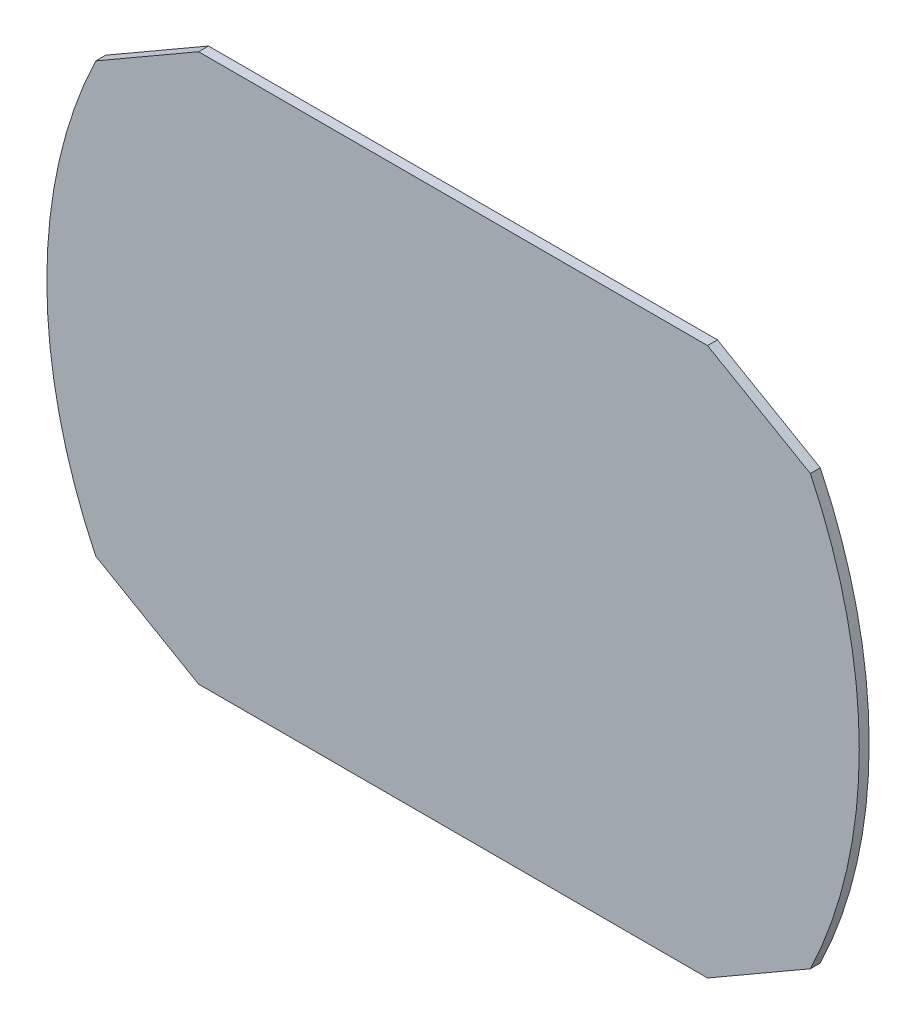
SolidWorks part; units mm, degrees
ref_plane "Front Plane" through (0, 0, 0) normal (0, 0, 1) x (1, 0, 0)
ref_plane "Top Plane" through (0, 0, 0) normal (0, 1, 0) x (1, 0, 0)
ref_plane "Right Plane" through (0, 0, 0) normal (1, 0, 0) x (0, 0, -1)
sketch "Sketch1" plane through (0, 0, 0) normal (0, 0, 1) x (1, 0, 0)
  line L0 (-65, 90) -> (-108.3013, 65)
  line L1 (-65, -90) -> (65, -90)
  line L3 (-65, 90) -> (65, 90)
  line L5 (-65, -90) -> (65, 90) construction
  line L6 (-65, 90) -> (65, -90) construction
  line L7 (-65, -90) -> (-108.3013, -65)
  line L8 (65, 90) -> (108.3013, 65)
  line L9 (65, -90) -> (108.3013, -65)
  arc A1 (-108.3013, 65) -> (-108.3013, -65) centre (26.8838, 0) ccw
  arc A4 (108.3013, 65) -> (108.3013, -65) centre (-26.8838, 0) cw
  point P0 (0, 0)
  point P7 (0, -90)
  dimension "D13" = 150
  dimension "D14" = 150
  dimension "D1" = 180
  dimension "D2" = 130
  dimension "D3" = 130
  dimension "D4" = 0
  dimension "D5" = 50
  dimension "D6" = 150
  dimension "D7" = 50
  dimension "D8" = 150
  dimension "D9" = 50
  dimension "D10" = 150
  dimension "D11" = 50
  dimension "D12" = 150
extrude "Boss-Extrude1" add sketch "Sketch1" along normal blind 3
sketch "Sketch2" plane through (0, 0, 3) normal (0, 0, 1) x (1, 0, 0)
  line L0 (-70.9808, 75) -> (70.9808, 75)
  line L1 (70.9808, 75) -> (103.1162, 56.4466)
  line L3 (65, 90) -> (-65, 90) construction
  line L4 (-70.9808, -75) -> (70.9808, -75)
  line L5 (70.9808, -75) -> (103.1162, -56.4466)
  line L6 (-65, -90) -> (65, -90) construction
  line L7 (108.3013, 65) -> (65, 90) construction
  line L8 (65, -90) -> (108.3013, -65) construction
  line L9 (-70.9808, 75) -> (-103.1162, 56.4466)
  line L10 (-70.9808, -75) -> (-103.1162, -56.4466)
  line L13 (-65, 90) -> (-108.3013, 65) construction
  line L15 (-108.3013, -65) -> (-65, -90) construction
  line L16 (-103.1162, 56.4466) -> (-103.1162, -56.4466)
  line L17 (103.1162, 56.4466) -> (103.1162, -56.4466)
  arc A0 (-108.3013, 65) -> (-108.3013, -65) centre (26.8838, 0) ccw construction
  arc A1 (108.3013, -65) -> (108.3013, 65) centre (-26.8838, 0) ccw construction
  point P24 (-123.1162, 0)
  point P28 (123.1162, 0)
  dimension "D1" = 15
  dimension "D2" = 10
  dimension "D3" = 20
  dimension "D4" = 15
  dimension "D5" = 20
  dimension "D7" = 10
  dimension "D8" = 10
  dimension "D10" = 10
sketch "Sketch3" plane through (0, 0, 0) normal (1, 0, 0) x (0, 0, -1)
  line L0 (-3, 90) -> (0, 90) construction
  line L1 (2, 85) -> (5.5, 85)
  line L2 (2, 85) -> (2, -85)
  line L3 (2, -85) -> (5.5, -85)
  line L4 (5.5, 85) -> (5.5, -85)
  line L5 (-3, -90) -> (0, -90) construction
  line L6 (-3, 65) -> (-3, -65) construction
  line L8 (-8.5, 82) -> (-5, 82)
  line L9 (-8.5, 82) -> (-8.5, -85)
  line L10 (-8.5, -85) -> (-5, -85)
  line L11 (-5, 82) -> (-5, -85)
  line L12 (0, -65) -> (0, 65) construction
  dimension "D1" = 5
  dimension "D2" = 5
  dimension "D3" = 5
  dimension "D4" = 3.5
  dimension "D5" = 8
  dimension "D6" = 5
  dimension "D7" = 5
  dimension "D8" = 3.5
extrude "Cut-Extrude4" [suppressed] cut sketch "Sketch2" against normal through all both and the other way through all
extrude "Cut-Extrude5" [suppressed] cut sketch "Sketch3" against normal through all both and the other way through all
sketch "Sketch7" [suppressed] plane through (0, 0, 0) normal (1, 0, 0) x (0, 0, -1)
  line L0 (-231.5, 65) -> (-231.5, -65) construction
  line L1 (-226.5, 45) -> (-13.5, 45)
  line L2 (-226.5, 45) -> (-226.5, 50)
  line L3 (-226.5, 50) -> (-13.5, 50)
  line L4 (-13.5, 45) -> (-13.5, 50)
  line L5 (-226.5, 45) -> (-13.5, 50) construction
  line L6 (-226.5, 50) -> (-13.5, 45) construction
  line L7 (-8.5, -65) -> (-8.5, 65) construction
  line L8 (0, 75) -> (-3, 75) construction
  point P0 (-120, 47.5)
  dimension "D1" = 5
  dimension "D2" = 5
  dimension "D3" = 5
  dimension "D4" = 25
extrude "Boss-Extrude4" [suppressed] add sketch "Sketch7" along normal up to surface and the other way up to surface
chamfer "Chamfer7" [suppressed] distance 6 angle 45
sketch "Sketch8" [suppressed] plane through (0, -75, 0) normal (0, 1, 0) x (1, 0, 0)
  line L0 (-78.8564, -8.5) -> (-108.3013, -8.5) construction
  line L1 (-2.5, -226.5) -> (2.5, -226.5)
  line L2 (-2.5, -226.5) -> (-2.5, -13.5)
  line L3 (-2.5, -13.5) -> (2.5, -13.5)
  line L4 (2.5, -226.5) -> (2.5, -13.5)
  line L5 (-2.5, -226.5) -> (2.5, -13.5) construction
  line L6 (-2.5, -13.5) -> (2.5, -226.5) construction
  line L7 (-108.3013, -231.5) -> (-73.6603, -231.5) construction
  point P0 (0, -120)
  dimension "D1" = 5
  dimension "D2" = 5
  dimension "D3" = 5
extrude "Boss-Extrude5" [suppressed] add sketch "Sketch8" along normal up to surface (120 mm away)
chamfer "Chamfer8" [suppressed] distance 6 angle 45
sketch "Sketch10" [suppressed] plane through (0, 0, 0) normal (1, 0, 0) x (0, 0, -1)
  line L0 (-240, -90) -> (0, -90) construction
  line L1 (-132.5, -75) -> (-107.5, -75)
  line L2 (-132.5, -75) -> (-132.5, -69)
  line L3 (-132.5, -69) -> (-107.5, -69)
  line L4 (-107.5, -75) -> (-107.5, -69)
  line L5 (-132.5, -75) -> (-107.5, -69) construction
  line L6 (-132.5, -69) -> (-107.5, -75) construction
  line L7 (-13.5, -75) -> (-226.5, -75) construction
  line L8 (-226.5, -69) -> (-13.5, -69) construction
  point P0 (-120, -72)
  point P7 (-120, -90)
  point P8 (-120, -75)
  dimension "D1" = 0
  dimension "D2" = 0
  dimension "D3" = 0
  dimension "D4" = 25
extrude "Cut-Extrude6" [suppressed] cut sketch "Sketch10" against normal blind 176 and the other way blind 23
sketch "Sketch12" [suppressed] plane through (0, 0, 0) normal (1, 0, 0) x (0, 0, -1)
  line L5 (-10, -64) -> (-230, -64)
  line L6 (-230, -64) -> (-230, -75)
  line L7 (-230, -75) -> (-14, -75)
  line L8 (-14, -75) -> (-14, -69)
  line L9 (-14, -69) -> (11, -69)
  line L10 (11, -69) -> (11, -75)
  line L11 (11, -75) -> (-10, -75)
  line L13 (-231.5, 56.4466) -> (-231.5, -56.4466) construction
  line L15 (0, -75) -> (-3, -75) construction
  line L16 (-3, -90) -> (0, -90) construction
  line L17 (-10, -75) -> (-10, -64)
  line L18 (-8.5, -85) -> (-8.5, -65) construction
  point P16 (-1.5, -69)
  point P19 (-1.5, -90)
  dimension "D1" = 11
  dimension "D2" = 1.5
  dimension "D3" = 1.5
  dimension "D4" = 0
  dimension "D5" = 0
  dimension "D6" = 25
  dimension "D7" = 6
  dimension "D8" = 6
extrude "Boss-Extrude6" [suppressed] add sketch "Sketch12" against normal blind 90
fillet "Fillet1" [suppressed] radius 10
fillet "Fillet2" [suppressed] radius 10
sketch "Sketch13" [suppressed] plane through (0, 0, 0) normal (1, 0, 0) x (0, 0, -1)
  line L0 (-3, 90) -> (0, 90) construction
  line L1 (0, 75) -> (-3, 75) construction
  circle A0 centre (-54.85, 62) radius 2.5
  circle A1 centre (51.85, 62) radius 2.5
  circle A2 centre (-1.5, 62) radius 2.5
  point P6 (-1.5, 90)
  dimension "D1" = 53.35
  dimension "D5" = 5
  dimension "D6" = 5
  dimension "D7" = 5
  dimension "D2" = 53.35
  dimension "D3" = 13
  dimension "D4" = 13
extrude "Cut-Extrude7" [suppressed] cut sketch "Sketch13" against normal through all
sketch "Sketch14" [suppressed] plane through (0, 50, 0) normal (0, 1, 0) x (1, 0, 0)
  line L0 (103.1162, -226.5) -> (-103.1162, -226.5) construction
  line L1 (-2.5, -226.5) -> (-2.5, -13.5) construction
  circle A0 centre (-52.5, -119.8) radius 2.5
  dimension "D1" = 5
  dimension "D2" = 106.7
  dimension "D3" = 50
extrude "Cut-Extrude8" [suppressed] cut sketch "Sketch14" against normal blind 47
sketch "Sketch15" [suppressed] plane through (-103.1162, 0, 0) normal (1, 0, 0) x (0, 0, -1)
  line L0 (-231.5, 56.4466) -> (-231.5, -56.4466) construction
  line L1 (-8.5, -56.4466) -> (-8.5, 56.4466) construction
  line L2 (-13.5, 39) -> (-226.5, 39) construction
  circle A0 centre (-172.99, 24) radius 2.5
  circle A1 centre (-67.25, 24) radius 2.5
  dimension "D1" = 58.51
  dimension "D3" = 5
  dimension "D4" = 5
  dimension "D2" = 58.75
  dimension "D5" = 15
extrude "Cut-Extrude9" [suppressed] cut sketch "Sketch15" against normal blind 36
sketch "Sketch16" [suppressed] plane through (0, -75, 0) normal (0, 1, 0) x (1, 0, 0)
  line L0 (70.9808, -8.5) -> (70.9808, -231.5) construction
  line L1 (23.5, -170) -> (29.5, -170)
  line L2 (23.5, -170) -> (23.5, -70)
  line L3 (23.5, -70) -> (29.5, -70)
  line L4 (29.5, -170) -> (29.5, -70)
  line L5 (8.5, -13.5) -> (8.5, -107.5) construction
  line L7 (39.5, -162.5) -> (59.5, -162.5)
  line L8 (39.5, -162.5) -> (39.5, -77.5)
  line L9 (39.5, -77.5) -> (59.5, -77.5)
  line L10 (59.5, -162.5) -> (59.5, -77.5)
  point P4 (23.5, -120)
  point P7 (70.9808, -120)
  point P14 (59.5, -120)
  dimension "D1" = 6
  dimension "D2" = 100
  dimension "D3" = 0
  dimension "D4" = 15
  dimension "D5" = 20
  dimension "D6" = 85
  dimension "D7" = 0
  dimension "D8" = 10
extrude "Cut-Extrude10" [suppressed] cut sketch "Sketch16" against normal blind 8
sketch "Sketch20" [suppressed] plane through (0, -75, 0) normal (0, 1, 0) x (1, 0, 0)
  line L0 (59.5, -77.5) -> (39.5, -77.5) construction
  line L1 (23, -70) -> (21, -70)
  line L2 (23, -70) -> (23, -170)
  line L3 (23, -170) -> (21, -170)
  line L4 (21, -70) -> (21, -170)
  line L5 (30, -70) -> (32, -70)
  line L6 (30, -70) -> (30, -170)
  line L7 (30, -170) -> (32, -170)
  line L8 (32, -70) -> (32, -170)
  line L9 (37.5, -77.5) -> (39, -77.5)
  line L10 (37.5, -77.5) -> (37.5, -162.5)
  line L11 (37.5, -162.5) -> (39, -162.5)
  line L12 (39, -77.5) -> (39, -162.5)
  line L13 (61.5, -162.5) -> (60, -162.5)
  line L14 (61.5, -162.5) -> (61.5, -77.5)
  line L15 (61.5, -77.5) -> (60, -77.5)
  line L16 (60, -162.5) -> (60, -77.5)
  line L17 (39.5, -162.5) -> (59.5, -162.5) construction
  line L18 (29.5, -70) -> (23.5, -70) construction
  line L19 (23.5, -170) -> (29.5, -170) construction
  line L20 (29.5, -170) -> (29.5, -70) construction
  line L21 (23.5, -70) -> (23.5, -170) construction
  line L22 (39.5, -77.5) -> (39.5, -162.5) construction
  line L23 (59.5, -162.5) -> (59.5, -77.5) construction
  dimension "D1" = 1.5
  dimension "D2" = 1.5
  dimension "D3" = 2
  dimension "D4" = 2
  dimension "D5" = 0.5
  dimension "D6" = 0.5
  dimension "D7" = 0.5
  dimension "D8" = 0.5
extrude "Boss-Extrude7" [suppressed] add sketch "Sketch20" along normal blind 8
sketch "Sketch21" [suppressed] plane through (0, 0, 170) normal (0, 0, 1) x (1, 0, 0)
  line L0 (22.5, -67) -> (21, -73.7542)
  line L1 (21, -67) -> (21, -75) construction
  line L2 (21, -73.7542) -> (21, -67)
  line L3 (21, -67) -> (22.5, -67)
  line L4 (30.5, -67) -> (32, -67)
  line L5 (32, -67) -> (32, -73.7542)
  line L6 (32, -67) -> (32, -75) construction
  line L7 (32, -73.7542) -> (30.5, -67)
  line L8 (38.5, -67) -> (37.5, -73.7542)
  line L9 (37.5, -67) -> (37.5, -75) construction
  line L10 (37.5, -73.7542) -> (37.5, -67)
  line L11 (37.5, -67) -> (38.5, -67)
  line L12 (60.5, -67) -> (61.5, -73.7542)
  line L13 (61.5, -67) -> (61.5, -75) construction
  line L14 (61.5, -73.7542) -> (61.5, -67)
  line L15 (61.5, -67) -> (60.5, -67)
  line L16 (21, -67) -> (23, -67) construction
  line L17 (30, -67) -> (32, -67) construction
  line L18 (37.5, -67) -> (39, -67) construction
  line L19 (60, -67) -> (61.5, -67) construction
  dimension "D1" = 1.5
  dimension "D2" = 1.5
  dimension "D3" = 1
  dimension "D4" = 1
extrude "Cut-Extrude11" [suppressed] cut sketch "Sketch21" against normal up to next
fillet "Fillet4" [suppressed] radius 0.25
fillet "Fillet5" [suppressed] radius 1
sketch "Sketch22" [suppressed] plane through (61.5, 0, 0) normal (1, 0, 0) x (0, 0, -1)
  line L0 (-162.5, -75) -> (-77.5, -75) construction
  line L1 (-130, -75) -> (-110, -75)
  line L2 (-130, -75) -> (-130, -65)
  line L3 (-130, -65) -> (-110, -65)
  line L4 (-110, -75) -> (-110, -65)
  point P6 (-120, -75)
  point P7 (-120, -75)
  dimension "D1" = 20
  dimension "D2" = 10
extrude "Cut-Extrude12" [suppressed] cut sketch "Sketch22" against normal blind 43
chamfer "Chamfer9" [suppressed] distance 1 angle 45
sketch "Sketch24" [suppressed] plane through (0, 50, 0) normal (0, 1, 0) x (1, 0, 0)
  line L0 (-17.9178, -104) -> (17.9178, -104)
  line L1 (103.1162, -13.5) -> (103.1162, -226.5) construction
  line L5 (-32.9693, -110.0691) -> (-29.9693, -110.0691)
  line L6 (-17.9178, -101.5752) -> (17.9178, -101.5752)
  line L7 (29.9693, -110.0691) -> (32.9693, -110.0691)
  arc A0 (-17.9178, -104) -> (-29.9693, -110.0691) centre (-17.9178, -119) ccw
  arc A1 (17.9178, -104) -> (29.9693, -110.0691) centre (17.9178, -119) cw
  arc A3 (-32.9693, -110.0691) -> (-17.9178, -101.5752) centre (-19.4178, -116.5) cw
  arc A4 (32.9693, -110.0691) -> (17.9178, -101.5752) centre (19.4178, -116.5) ccw
  point P3 (0, -104)
  point P6 (103.1162, -120)
  dimension "D3" = 15
  dimension "D4" = 15
  dimension "D5" = 1.5
  dimension "D7" = 15
  dimension "D8" = 15
  dimension "D11" = 3
  dimension "D12" = 3
  dimension "D1" = 0
  dimension "D2" = 16
  dimension "D6" = 2.5
  dimension "D9" = 1.5
  dimension "D10" = 2.5
extrude "Boss-Extrude8" [suppressed] add sketch "Sketch24" along normal blind 8
fillet "Fillet6" [suppressed] radius 1
fillet "Fillet7" [suppressed] radius 1
sketch "Sketch25" [suppressed] plane through (0, -64, 0) normal (0, 1, 0) x (1, 0, 0)
  line L0 (-90, -10) -> (-7.5993, -10) construction
  line L1 (-2.5, -13.5) -> (-2.5, -226.5) construction
  line L3 (-90, -230) -> (-7.5993, -230) construction
  circle A0 centre (-48.7997, -46.5) radius 35
  circle A1 centre (-48.7997, -120) radius 35
  circle A2 centre (-48.7997, -193.5) radius 35
  point P9 (-48.7997, -10)
  point P13 (-2.5, -120)
  dimension "D1" = 70
  dimension "D2" = 70
  dimension "D3" = 70
  dimension "D4" = 36.5
  dimension "D5" = 36.5
extrude "Cut-Extrude13" [suppressed] cut sketch "Sketch25" against normal blind 5
sketch "Sketch26" [suppressed] plane through (0, 50, 0) normal (0, 1, 0) x (1, 0, 0)
  line L0 (70.9808, -8.5) -> (70.9808, -231.5) construction
  line L1 (73.9808, -155) -> (98.9808, -155)
  line L2 (73.9808, -155) -> (73.9808, -85)
  line L3 (73.9808, -85) -> (98.9808, -85)
  line L4 (98.9808, -155) -> (98.9808, -85)
  line L5 (73.9808, -155) -> (98.9808, -85) construction
  line L6 (73.9808, -85) -> (98.9808, -155) construction
  line L7 (108.3013, -231.5) -> (108.3013, -8.5) construction
  point P0 (86.4808, -120)
  point P9 (108.3013, -120)
  dimension "D1" = 70
  dimension "D2" = 25
  dimension "D3" = 3
  dimension "D4" = 0
extrude "Cut-Extrude14" [suppressed] cut sketch "Sketch26" against normal blind 12.5 from offset 105 offset against normal yes
sketch "Sketch27" [suppressed] plane through (0, -67.5, 0) normal (0, 1, 0) x (1, 0, 0)
  line L0 (83.9711, -155) -> (98.9808, -155) construction
  line L1 (83.9711, -85) -> (73.9711, -85)
  line L2 (83.9711, -85) -> (83.9711, -155)
  line L3 (83.9711, -155) -> (73.9711, -155)
  line L4 (73.9711, -85) -> (73.9711, -155)
  dimension "D1" = 10
extrude "Boss-Extrude9" [suppressed] add sketch "Sketch27" against normal blind 9
fillet "Fillet8" [suppressed] radius 1
sketch "Sketch28" [suppressed] plane through (0, 0, 155) normal (0, 0, 1) x (1, 0, 0)
  line L0 (73.9711, -73.2735) -> (83.9711, -67.5)
  line L2 (73.9711, -73.2735) -> (73.9711, -67.5)
  line L3 (73.9711, -67.5) -> (83.9711, -67.5)
extrude "Cut-Extrude15" [suppressed] cut sketch "Sketch28" against normal blind 10 from offset 30 offset against normal yes
fillet "Fillet9" [suppressed] radius 1
fillet "Fillet10" [suppressed] radius 2
chamfer "Chamfer10" [suppressed] distance 1 angle 45
sketch "Sketch29" plane through (0, 0, 0) normal (0, 0, 1) x (1, 0, 0)
  line L1 (-135.4816, 0) -> (144.3449, 0)
  line L2 (-135.4816, 0) -> (-135.4816, -99.522)
  line L3 (-135.4816, -99.522) -> (144.3449, -99.522)
  line L4 (144.3449, 0) -> (144.3449, -99.522)
extrude "Cut-Extrude16" [suppressed] cut sketch "Sketch29" against normal through all both and the other way through all
sketch "Sketch30" [suppressed] plane through (0, 0, 0) normal (0, -1, 0) x (1, 0, 0)
  line L0 (-123.1162, 231.5) -> (-103.1162, 231.5) construction
  line L1 (-118.1162, 191.5) -> (-108.1162, 191.5)
  line L2 (-118.1162, 191.5) -> (-118.1162, 48.5)
  line L3 (-118.1162, 48.5) -> (-108.1162, 48.5)
  line L4 (-108.1162, 191.5) -> (-108.1162, 48.5)
  line L5 (108.1162, 191.5) -> (118.1162, 191.5)
  line L6 (108.1162, 191.5) -> (108.1162, 48.5)
  line L7 (108.1162, 48.5) -> (118.1162, 48.5)
  line L8 (118.1162, 191.5) -> (118.1162, 48.5)
  line L9 (-103.1162, 8.5) -> (-123.1162, 8.5) construction
  line L10 (103.1162, 231.5) -> (123.1162, 231.5) construction
  line L11 (123.1162, 8.5) -> (103.1162, 8.5) construction
  line L12 (-123.1162, 8.5) -> (-123.1162, 231.5) construction
  line L13 (-103.1162, 231.5) -> (-103.1162, 8.5) construction
  line L14 (103.1162, 226.5) -> (103.1162, 13.5) construction
  line L15 (123.1162, 231.5) -> (123.1162, 8.5) construction
  dimension "D1" = 40
  dimension "D2" = 40
  dimension "D3" = 40
  dimension "D4" = 40
  dimension "D5" = 5
  dimension "D6" = 5
  dimension "D7" = 5
  dimension "D8" = 5
extrude "Cut-Extrude17" [suppressed] cut sketch "Sketch30" against normal blind 20
chamfer "Chamfer11" [suppressed] distance 3 angle 45
sketch "Sketch32" [suppressed] plane through (0, 0, 3) normal (0, 0, 1) x (1, 0, 0)
  line L0 (-53, 90) -> (-53, 88)
  line L1 (65, 90) -> (-65, 90) construction
  line L2 (-53, 88) -> (-60, 88)
  line L3 (-60, 88) -> (-60, 84.5)
  line L4 (-60, 84.5) -> (-53, 84.5)
  line L5 (-53, 84.5) -> (-53, 82.5)
  line L6 (-53, 82.5) -> (-60, 82.5)
  line L7 (-60, 82.5) -> (-60, 75)
  line L8 (-70.9808, 75) -> (70.9808, 75) construction
  line L9 (-60, 75) -> (60, 75)
  line L10 (60, 75) -> (60, 82.5)
  line L11 (60, 82.5) -> (53, 82.5)
  line L12 (53, 82.5) -> (53, 84.5)
  line L13 (53, 84.5) -> (60, 84.5)
  line L14 (60, 84.5) -> (60, 88)
  line L15 (60, 88) -> (53, 88)
  line L16 (53, 88) -> (53, 90)
  line L17 (53, 90) -> (-53, 90)
  dimension "D1" = 12
  dimension "D2" = 5
  dimension "D3" = 7
  dimension "D4" = 5
  dimension "D5" = 2
  dimension "D6" = 2
  dimension "D7" = 3.5
  dimension "D8" = 2
  dimension "D9" = 2
  dimension "D10" = 3.5
extrude "Cut-Extrude19" [suppressed] cut sketch "Sketch32" against normal through all from offset 8.5 offset against normal yes
fillet "Fillet11" [suppressed] radius 1
sketch "Sketch33" plane through (0, 0, 3) normal (0, 0, 1) x (1, 0, 0)
  line L1 (65, 90) -> (-65, 90) construction
  circle A0 centre (0, 82.5) radius 2
  dimension "D1" = 7.5
  dimension "D2" = 4
extrude "Cut-Extrude20" [suppressed] cut sketch "Sketch33" against normal blind 4.5
chamfer "Chamfer12" [suppressed] distance 1 angle 45
sketch "Sketch34" plane through (0, 0, 0) normal (1, 0, 0) x (0, 0, -1)
  line L0 (0, 65) -> (0, 90) construction
  line L1 (-3, 90) -> (0, 90)
  line L2 (-3, 90) -> (-3, 83)
  line L3 (-3, 83) -> (0, 83)
  line L4 (0, 90) -> (0, 83)
  line L5 (0, -90) -> (0, -65) construction
  line L7 (-3, -90) -> (0, -90)
  line L8 (-3, -90) -> (-3, -83)
  line L9 (-3, -83) -> (0, -83)
  line L10 (0, -90) -> (0, -83)
  dimension "D1" = 7
  dimension "D2" = 7
extrude "Cut-Extrude21" cut sketch "Sketch34" against normal through all both and the other way through all
equation "\"`\"=64"
